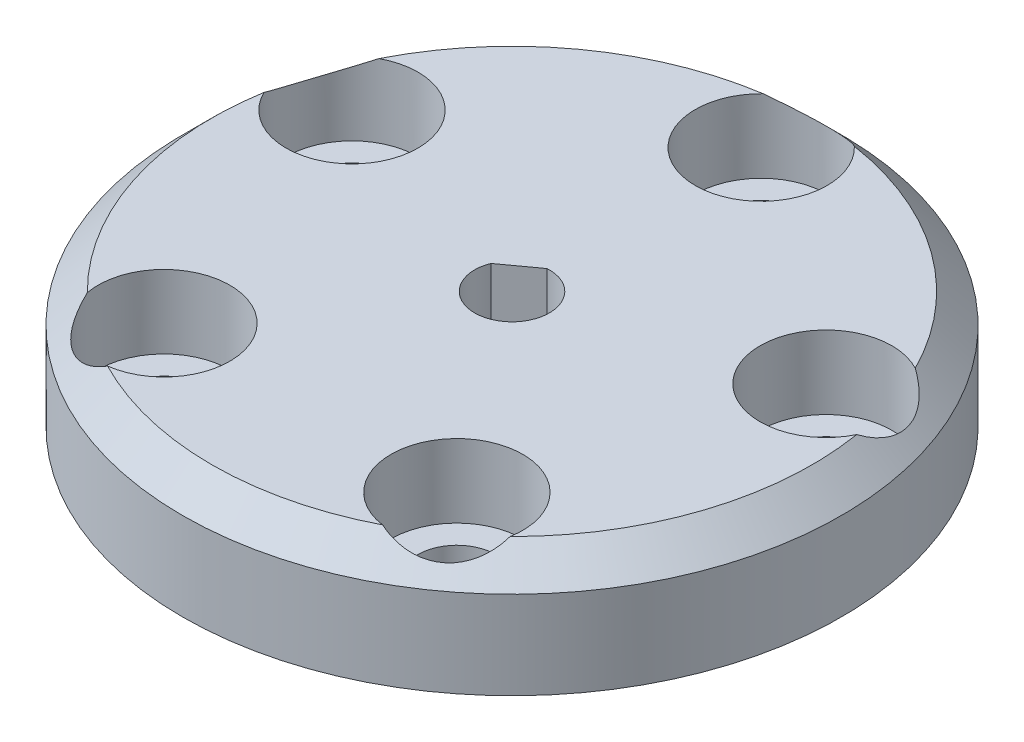
SolidWorks part; units mm, degrees
ref_plane "Front Plane" through (0, 0, 0) normal (0, 0, 1) x (1, 0, 0)
ref_plane "Top Plane" through (0, 0, 0) normal (0, 1, 0) x (1, 0, 0)
ref_plane "Right Plane" through (0, 0, 0) normal (1, 0, 0) x (0, 0, -1)
sketch "Sketch1" plane through (0, 0, 0) normal (0, 1, 0) x (1, 0, 0)
  line L1 (10, -13.7638) -> (16.1803, 5.2573) construction
  line L2 (16.1803, 5.2573) -> (0, 17.013) construction
  line L3 (0, 17.013) -> (-16.1803, 5.2573) construction
  line L4 (-16.1803, 5.2573) -> (-10, -13.7638) construction
  line L5 (-10, -13.7638) -> (10, -13.7638) construction
  circle A0 centre (0, 0) radius 13.7638 construction
  circle A15 centre (0, 0) radius 25.013 construction
  circle A16 centre (0, 17.013) radius 8 construction
  circle A17 centre (16.1803, 5.2573) radius 8 construction
  circle A18 centre (10, -13.7638) radius 8 construction
  circle A19 centre (-10, -13.7638) radius 8 construction
  circle A22 centre (-16.1803, 5.2573) radius 8 construction
  circle A23 centre (0, 0) radius 22.5
  circle A24 centre (0, 17.013) radius 2.65
  circle A25 centre (-16.1803, 5.2573) radius 2.65
  circle A26 centre (-10, -13.7638) radius 2.65
  circle A27 centre (10, -13.7638) radius 2.65
  circle A28 centre (16.1803, 5.2573) radius 2.65
  dimension "D1" = 16
  dimension "D2" = 20
  dimension "D3" = 45
  dimension "D4" = 5.3
extrude "Boss-Extrude1" add sketch "Sketch1" along normal blind 8
sketch "Sketch2" plane through (0, 8, 0) normal (0, 1, 0) x (1, 0, 0)
  circle A0 centre (-16.1803, 5.2573) radius 4.5
  circle A1 centre (0, 17.013) radius 4.5
  circle A2 centre (16.1803, 5.2573) radius 4.5
  circle A3 centre (10, -13.7638) radius 4.5
  circle A4 centre (-10, -13.7638) radius 4.5
  dimension "D1" = 9
extrude "Cut-Extrude1" cut sketch "Sketch2" against normal blind 5
chamfer "Chamfer1" distance 2 angle 45 1 edges at (0, 8, 22.5)
sketch "Sketch3" plane through (0, 0, 0) normal (0, -1, 0) x (1, 0, 0)
  line L0 (-0.1545, -2.5453) -> (-2.373, -0.9335)
  line L1 (-0.1545, -2.5453) -> (-2.373, -0.9335) construction
  arc A0 (-0.1545, -2.5453) -> (-2.373, -0.9335) centre (0, 0) ccw
  point P1 (1.4989, 2.063)
  dimension "D2" = 4.7
extrude "Cut-Extrude3" cut sketch "Sketch3" against normal through all contours A0 L0
